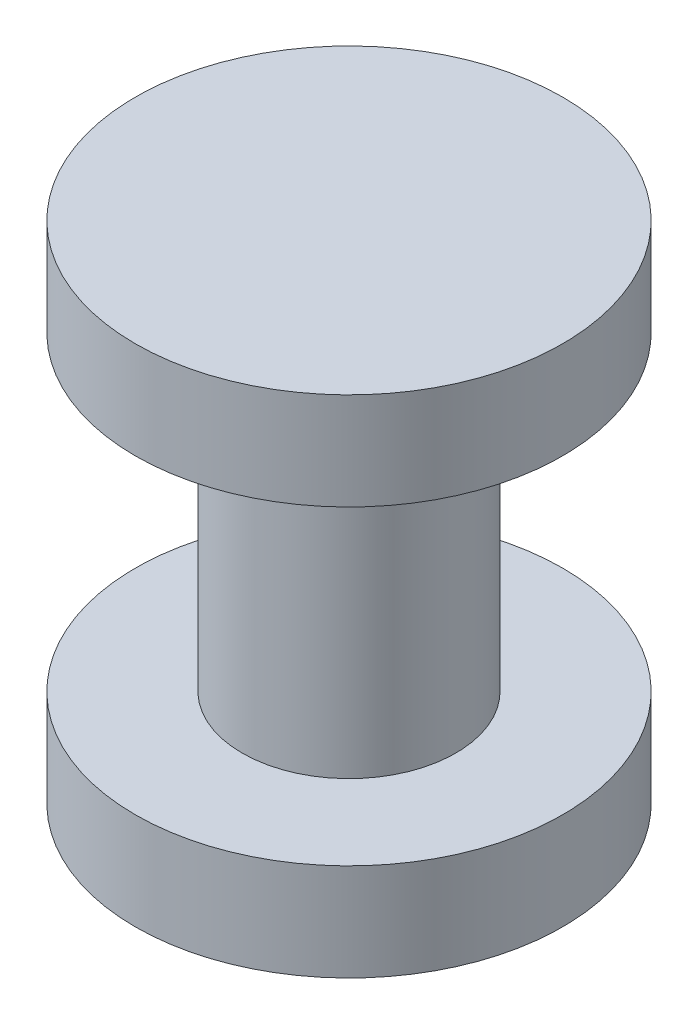
SolidWorks part; units mm, degrees
ref_plane "前视基准面" through (0, 0, 0) normal (0, 0, 1) x (1, 0, 0)
ref_plane "上视基准面" through (0, 0, 0) normal (0, 1, 0) x (1, 0, 0)
ref_plane "右视基准面" through (0, 0, 0) normal (1, 0, 0) x (0, 0, -1)
other "Configuration Table"
sketch "草图1" plane through (0, 0, 0) normal (0, 1, 0) x (1, 0, 0)
  circle A0 centre (0, 0) radius 5.5
  circle A1 centre (0, 0) radius 11
  dimension "D1" = 5.5
  dimension "D2" = 22
extrude "凸台-拉伸3" add sketch "草图1" along normal mid plane 26 contours A1
extrude "切除-拉伸1" cut sketch "草图1<10>" along normal mid plane 16
sketch "草图1<10>" plane through (0, 0, 0) normal (0, 1, 0) x (1, 0, 0) same geometry as "草图1"
